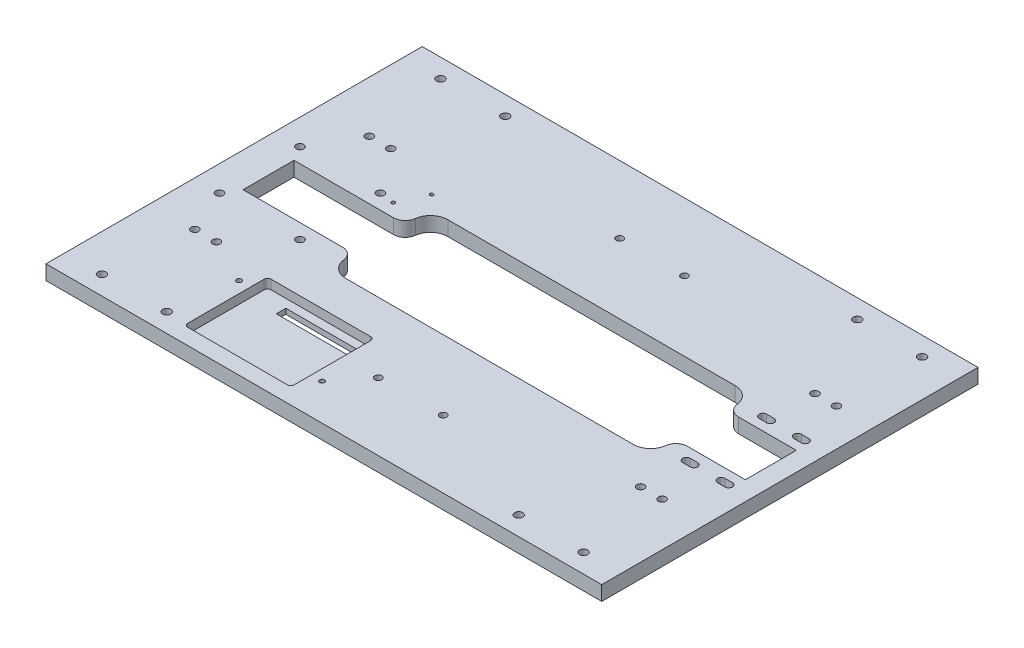
SolidWorks part; units mm, degrees
ref_plane "Front Plane" through (0, 0, 0) normal (0, 0, 1) x (1, 0, 0)
ref_plane "Top Plane" through (0, 0, 0) normal (0, 1, 0) x (1, 0, 0)
ref_plane "Right Plane" through (0, 0, 0) normal (1, 0, 0) x (0, 0, -1)
sketch "Sketch1" plane through (0, 0, 0) normal (0, 1, 0) x (1, 0, 0)
  line L1 (-240, 162.5) -> (240, 162.5)
  line L2 (-240, 162.5) -> (-240, -162.5)
  line L3 (-240, -162.5) -> (240, -162.5)
  line L4 (240, 162.5) -> (240, -162.5)
  line L5 (-240, 162.5) -> (240, -162.5) construction
  line L6 (-240, -162.5) -> (240, 162.5) construction
  point P0 (0, 0)
  dimension "D1" = 480
  dimension "D2" = 325
extrude "Boss-Extrude1" add sketch "Sketch1" along normal blind 12.6
sketch "Sketch2" plane through (0, 0, 0) normal (0, -1, 0) x (1, 0, 0)
  circle A0 centre (44.7486, -104.2) radius 3
  circle A1 centre (-11.2514, -104.2) radius 3
  circle A2 centre (44.7486, 104.2) radius 3
  circle A3 centre (-11.2514, 104.2) radius 3
extrude "Cut-Extrude1" cut sketch "Sketch2" against normal up to next
sketch "Sketch3" plane through (0, 0, 0) normal (0, -1, 0) x (1, 0, 0)
  line L0 (-192.4406, 0) -> (188.5847, 0) construction
  line L1 (163.5847, 44) -> (-114.2887, 44)
  line L2 (163.5847, 44) -> (163.5847, 22)
  line L3 (163.5847, -44) -> (-114.2887, -44)
  line L5 (-114.2887, -44) -> (-114.2887, -22)
  line L6 (-114.2887, -22) -> (-210.2887, -22)
  line L7 (-114.2887, 44) -> (-114.2887, 22)
  line L8 (-114.2887, 22) -> (-210.2887, 22)
  line L9 (-210.2887, 22) -> (-210.2887, -22)
  line L10 (163.5847, 22) -> (223.5847, 22)
  line L11 (223.5847, 22) -> (223.5847, -22)
  line L12 (223.5847, -22) -> (163.5847, -22)
  line L13 (163.5847, -22) -> (163.5847, -44)
  point P0 (0, 0)
  point P1 (-210.2887, 0)
  dimension "D2" = 96
  dimension "D1" = 22
  dimension "D5" = 60
extrude "Cut-Extrude2" cut sketch "Sketch3" against normal up to next
fillet "Fillet1" radius 10 2 edges at (-114.2887, 6.3, 22) (-114.2887, 6.3, -22)
sketch "Sketch4" plane through (0, 0, 0) normal (0, -1, 0) x (1, 0, 0)
  circle A12 centre (-148.4257, -34.75) radius 3.3
  circle A13 centre (-148.4257, 34.75) radius 3.3
  circle A14 centre (-217.9257, 34.75) radius 3.3
  circle A15 centre (-217.9257, -34.75) radius 3.3
extrude "Cut-Extrude3" cut sketch "Sketch4" against normal up to next
fillet "Fillet2" radius 10 2 edges at (163.5847, 6.3, -22) (163.5847, 6.3, 22)
sketch "Sketch7" plane through (0, 12.6, 0) normal (0, 1, 0) x (1, 0, 0)
  circle A0 centre (208, -146.2) radius 2.25
  circle A1 centre (152, -146.2) radius 2.25
  circle A2 centre (-152, -146.2) radius 2.25
  circle A3 centre (-208, -146.2) radius 2.25
  circle A4 centre (-208, 146.2) radius 2.25
  circle A5 centre (-152, 146.2) radius 2.25
  circle A6 centre (208, 146.2) radius 2.25
  circle A7 centre (152, 146.2) radius 2.25
  circle A9 centre (-143.9752, -91.7292) radius 2.2102
  circle A10 centre (-32.9752, -131.1304) radius 2.1044
  dimension "D1" = 4.5
extrude "Cut-Extrude7" cut sketch "Sketch7" against normal up to next
sketch "Sketch8" plane through (0, 12.6, 0) normal (0, 1, 0) x (1, 0, 0)
  circle A0 centre (208, 146.2) radius 3.5
  circle A1 centre (152, 146.2) radius 3.5
  circle A2 centre (-152, 146.2) radius 3.5
  circle A3 centre (-208, 146.2) radius 3.5
  circle A4 centre (208, -146.2) radius 3.5
  circle A5 centre (152, -146.2) radius 3.5
  circle A6 centre (-208, -146.2) radius 3.5
  circle A7 centre (-152, -146.2) radius 3.5
  dimension "D1" = 7
extrude "Cut-Extrude8" cut sketch "Sketch8" against normal blind 6
sketch "Sketch9" plane through (0, 12.6, 0) normal (0, 1, 0) x (1, 0, 0)
  line L1 (-131.2752, -76.7932) -> (-45.2752, -76.7932)
  line L2 (-134.2752, -79.7932) -> (-134.2752, -145.7932)
  line L3 (-131.2752, -148.7932) -> (-45.2752, -148.7932)
  line L4 (-42.2752, -79.7932) -> (-42.2752, -145.7932)
  arc A0 (-134.2752, -145.7932) -> (-131.2752, -148.7932) centre (-131.2752, -145.7932) ccw
  arc A1 (-45.2752, -148.7932) -> (-42.2752, -145.7932) centre (-45.2752, -145.7932) ccw
  arc A2 (-45.2752, -76.7932) -> (-42.2752, -79.7932) centre (-45.2752, -79.7932) cw
  arc A3 (-131.2752, -76.7932) -> (-134.2752, -79.7932) centre (-131.2752, -79.7932) ccw
  dimension "D5" = 3
sketch "Sketch12" plane through (0, 0, 0) normal (0, -1, 0) x (1, 0, 0)
  circle A0 centre (-135.8148, -33.2631) radius 1.5
  circle A1 centre (-125.2148, -55.8631) radius 1.5
extrude "Cut-Extrude11" cut sketch "Sketch12" against normal up to next
fillet "Fillet3" radius 15 4 edges at (163.5847, 6.3, 44) (163.5847, 6.3, -44) (-114.2887, 6.3, 44) (-114.2887, 6.3, -44)
extrude "Cut-Extrude12" cut sketch "Sketch9" against normal blind 8
sketch "Sketch14" plane through (0, 4.6, 0) normal (0, 1, 0) x (1, 0, 0)
  line L1 (-111.1572, -84.1633) -> (-47.573, -84.1633)
  line L2 (-111.1572, -84.1633) -> (-111.1572, -92.4204)
  line L3 (-111.1572, -92.4204) -> (-47.573, -92.4204)
  line L4 (-47.573, -84.1633) -> (-47.573, -92.4204)
extrude "Cut-Extrude13" cut sketch "Sketch14" against normal through all
sketch "Sketch15" plane through (0, 12.6, 0) normal (0, 1, 0) x (1, 0, 0)
  circle A0 centre (-201.3752, -72.5) radius 3.25 construction
  circle A1 centre (-182.8647, -72.5) radius 3.25 construction
  circle A2 centre (-195.7918, 72.5) radius 3.25 construction
  circle A3 centre (-177.2813, 72.5) radius 3.25 construction
  circle A4 centre (189.2082, 72.5) radius 3.25 construction
  circle A5 centre (207.7187, 72.5) radius 3.25 construction
  circle A6 centre (183.6248, -72.5) radius 3.25 construction
  circle A7 centre (202.1353, -72.5) radius 3.25 construction
  circle A8 centre (-201.3752, -72.5) radius 3.25
  circle A9 centre (-182.8647, -72.5) radius 3.25
  circle A10 centre (-195.7918, 72.5) radius 3.25
  circle A11 centre (-177.2813, 72.5) radius 3.25
  circle A12 centre (189.2082, 72.5) radius 3.25
  circle A13 centre (207.7187, 72.5) radius 3.25
  circle A14 centre (183.6248, -72.5) radius 3.25
  circle A15 centre (202.1353, -72.5) radius 3.25
extrude "Cut-Extrude14" cut sketch "Sketch15" against normal up to next
sketch "Sketch16" plane through (0, 12.6, 0) normal (0, 1, 0) x (1, 0, 0)
  line L0 (183.6729, -33) -> (186.9229, -33) construction
  line L1 (213.6729, -33) -> (216.9229, -33) construction
  line L2 (183.6729, 33) -> (186.9229, 33) construction
  line L3 (213.6729, 33) -> (216.9229, 33) construction
  line L4 (183.6729, -36.25) -> (190.1729, -36.25)
  line L5 (183.6729, -29.75) -> (190.1729, -29.75)
  line L6 (213.6729, -36.25) -> (220.1729, -36.25)
  line L7 (213.6729, -29.75) -> (220.1729, -29.75)
  line L8 (183.6729, 29.75) -> (190.1729, 29.75)
  line L9 (183.6729, 36.25) -> (190.1729, 36.25)
  line L10 (213.6729, 29.75) -> (220.1729, 29.75)
  line L11 (213.6729, 36.25) -> (220.1729, 36.25)
  arc A4 (213.6729, -29.75) -> (213.6729, -36.25) centre (213.6729, -33) ccw
  arc A5 (183.6729, -29.75) -> (183.6729, -36.25) centre (183.6729, -33) ccw
  arc A6 (183.6729, 36.25) -> (183.6729, 29.75) centre (183.6729, 33) ccw
  arc A7 (213.6729, 36.25) -> (213.6729, 29.75) centre (213.6729, 33) ccw
  arc A8 (190.1729, -36.25) -> (190.1729, -29.75) centre (190.1729, -33) ccw
  arc A9 (220.1729, -36.25) -> (220.1729, -29.75) centre (220.1729, -33) ccw
  arc A10 (220.1729, 29.75) -> (220.1729, 36.25) centre (220.1729, 33) ccw
  arc A11 (190.1729, 29.75) -> (190.1729, 36.25) centre (190.1729, 33) ccw
  dimension "D1" = 6.5
  dimension "D2" = 6.5
  dimension "D3" = 6.5
  dimension "D4" = 6.5
extrude "Cut-Extrude15" cut sketch "Sketch16" against normal up to next
sketch "Sketch17" plane through (0, 12.6, 0) normal (0, 1, 0) x (1, 0, 0)
  line L4 (240, -162.5) -> (240, 162.5)
  line L5 (240, 162.5) -> (-240, 162.5)
  line L6 (-240, 162.5) -> (-240, -162.5)
  line L7 (-240, -162.5) -> (240, -162.5)
  line L8 (240, -162.5) -> (240, 162.5)
  line L9 (240, 162.5) -> (-240, 162.5)
  line L10 (-240, 162.5) -> (-240, -162.5)
  line L11 (-240, -162.5) -> (240, -162.5)
  line L14 (220.1729, -29.75) -> (213.6729, -29.75)
  line L15 (213.6729, -36.25) -> (220.1729, -36.25)
  line L16 (220.1729, -29.75) -> (213.6729, -29.75)
  line L17 (213.6729, -36.25) -> (220.1729, -36.25)
  line L18 (190.1729, -29.75) -> (183.6729, -29.75)
  line L19 (183.6729, -36.25) -> (190.1729, -36.25)
  line L20 (190.1729, -29.75) -> (183.6729, -29.75)
  line L21 (183.6729, -36.25) -> (190.1729, -36.25)
  line L22 (220.1729, 36.25) -> (213.6729, 36.25)
  line L23 (213.6729, 29.75) -> (220.1729, 29.75)
  line L24 (220.1729, 36.25) -> (213.6729, 36.25)
  line L25 (213.6729, 29.75) -> (220.1729, 29.75)
  line L26 (190.1729, 36.25) -> (183.6729, 36.25)
  line L27 (183.6729, 29.75) -> (190.1729, 29.75)
  line L28 (190.1729, 36.25) -> (183.6729, 36.25)
  line L29 (183.6729, 29.75) -> (190.1729, 29.75)
  line L33 (-134.2752, -79.7932) -> (-134.2752, -145.7932)
  line L34 (-45.2752, -76.7932) -> (-131.2752, -76.7932)
  line L35 (-42.2752, -145.7932) -> (-42.2752, -79.7932)
  line L36 (148.7654, 44) -> (-99.4693, 44)
  line L37 (223.5847, 22) -> (173.5847, 22)
  line L38 (223.5847, -22) -> (223.5847, 22)
  line L39 (173.5847, -22) -> (223.5847, -22)
  line L40 (-99.4693, -44) -> (148.7654, -44)
  line L41 (-210.2887, -22) -> (-124.2887, -22)
  line L42 (-210.2887, 22) -> (-210.2887, -22)
  line L43 (-124.2887, 22) -> (-210.2887, 22)
  line L44 (148.7654, 44) -> (-99.4693, 44)
  line L45 (223.5847, 22) -> (173.5847, 22)
  line L46 (223.5847, -22) -> (223.5847, 22)
  line L47 (173.5847, -22) -> (223.5847, -22)
  line L48 (-99.4693, -44) -> (148.7654, -44)
  line L49 (-210.2887, -22) -> (-124.2887, -22)
  line L50 (-210.2887, 22) -> (-210.2887, -22)
  line L51 (-124.2887, 22) -> (-210.2887, 22)
  line L52 (-131.2752, -148.7932) -> (-45.2752, -148.7932)
  line L53 (-134.2752, -79.7932) -> (-134.2752, -145.7932)
  line L54 (-45.2752, -76.7932) -> (-131.2752, -76.7932)
  line L55 (-42.2752, -145.7932) -> (-42.2752, -79.7932)
  line L56 (-131.2752, -148.7932) -> (-45.2752, -148.7932)
  line L58 (-111.1572, -84.1633) -> (-111.1572, -92.4204)
  line L59 (-47.573, -84.1633) -> (-111.1572, -84.1633)
  line L60 (-47.573, -92.4204) -> (-47.573, -84.1633)
  line L61 (-111.1572, -92.4204) -> (-47.573, -92.4204)
  line L62 (-111.1572, -84.1633) -> (-111.1572, -92.4204)
  line L63 (-47.573, -84.1633) -> (-111.1572, -84.1633)
  line L64 (-47.573, -92.4204) -> (-47.573, -84.1633)
  line L65 (-111.1572, -92.4204) -> (-47.573, -92.4204)
  circle A0 centre (208, 146.2) radius 3.5 construction
  circle A1 centre (208, 146.2) radius 2.25 construction
  circle A2 centre (152, 146.2) radius 3.5 construction
  circle A3 centre (152, 146.2) radius 2.25 construction
  circle A4 centre (-11.2514, 104.2) radius 3 construction
  circle A5 centre (44.7486, 104.2) radius 3 construction
  circle A6 centre (207.7187, 72.5) radius 3.25 construction
  circle A7 centre (189.2082, 72.5) radius 3.25 construction
  circle A8 centre (202.1353, -72.5) radius 3.25 construction
  circle A9 centre (183.6248, -72.5) radius 3.25 construction
  circle A10 centre (208, -146.2) radius 3.5 construction
  circle A11 centre (208, -146.2) radius 2.25 construction
  circle A12 centre (152, -146.2) radius 3.5 construction
  circle A13 centre (152, -146.2) radius 2.25 construction
  circle A14 centre (44.7486, -104.2) radius 3 construction
  circle A15 centre (-11.2514, -104.2) radius 3 construction
  circle A16 centre (-152, -146.2) radius 2.25 construction
  circle A17 centre (-152, -146.2) radius 3.5 construction
  circle A18 centre (-208, -146.2) radius 3.5 construction
  circle A19 centre (-208, -146.2) radius 2.25 construction
  circle A20 centre (-182.8647, -72.5) radius 3.25 construction
  circle A21 centre (-201.3752, -72.5) radius 3.25 construction
  circle A22 centre (-217.9257, -34.75) radius 3.3 construction
  circle A23 centre (-148.4257, -34.75) radius 3.3 construction
  circle A24 centre (-125.2148, 55.8631) radius 1.5 construction
  circle A25 centre (-135.8148, 33.2631) radius 1.5 construction
  circle A26 centre (-148.4257, 34.75) radius 3.3 construction
  circle A27 centre (-217.9257, 34.75) radius 3.3 construction
  circle A28 centre (-177.2813, 72.5) radius 3.25 construction
  circle A29 centre (-195.7918, 72.5) radius 3.25 construction
  circle A30 centre (-152, 146.2) radius 2.25 construction
  circle A31 centre (-152, 146.2) radius 3.5 construction
  circle A32 centre (-208, 146.2) radius 2.25 construction
  circle A33 centre (-208, 146.2) radius 3.5 construction
  circle A34 centre (208, 146.2) radius 3.5
  circle A35 centre (208, 146.2) radius 2.25
  circle A36 centre (152, 146.2) radius 3.5
  circle A37 centre (152, 146.2) radius 2.25
  circle A38 centre (-11.2514, 104.2) radius 3
  circle A39 centre (44.7486, 104.2) radius 3
  circle A40 centre (207.7187, 72.5) radius 3.25
  circle A41 centre (189.2082, 72.5) radius 3.25
  circle A42 centre (202.1353, -72.5) radius 3.25
  circle A43 centre (183.6248, -72.5) radius 3.25
  circle A44 centre (208, -146.2) radius 3.5
  circle A45 centre (208, -146.2) radius 2.25
  circle A46 centre (152, -146.2) radius 3.5
  circle A47 centre (152, -146.2) radius 2.25
  circle A48 centre (44.7486, -104.2) radius 3
  circle A49 centre (-11.2514, -104.2) radius 3
  circle A50 centre (-152, -146.2) radius 2.25
  circle A51 centre (-152, -146.2) radius 3.5
  circle A52 centre (-208, -146.2) radius 3.5
  circle A53 centre (-208, -146.2) radius 2.25
  circle A54 centre (-182.8647, -72.5) radius 3.25
  circle A55 centre (-201.3752, -72.5) radius 3.25
  circle A56 centre (-217.9257, -34.75) radius 3.3
  circle A57 centre (-148.4257, -34.75) radius 3.3
  circle A58 centre (-125.2148, 55.8631) radius 1.5
  circle A59 centre (-135.8148, 33.2631) radius 1.5
  circle A60 centre (-148.4257, 34.75) radius 3.3
  circle A61 centre (-217.9257, 34.75) radius 3.3
  circle A62 centre (-177.2813, 72.5) radius 3.25
  circle A63 centre (-195.7918, 72.5) radius 3.25
  circle A64 centre (-152, 146.2) radius 2.25
  circle A65 centre (-152, 146.2) radius 3.5
  circle A66 centre (-208, 146.2) radius 2.25
  circle A67 centre (-208, 146.2) radius 3.5
  circle A68 centre (-32.9752, -131.1304) radius 2.1044 construction
  circle A69 centre (-143.9752, -91.7292) radius 2.2102 construction
  arc A70 (213.6729, -29.75) -> (213.6729, -36.25) centre (213.6729, -33) ccw
  arc A71 (220.1729, -36.25) -> (220.1729, -29.75) centre (220.1729, -33) ccw
  arc A72 (213.6729, -29.75) -> (213.6729, -36.25) centre (213.6729, -33) ccw
  arc A73 (220.1729, -36.25) -> (220.1729, -29.75) centre (220.1729, -33) ccw
  arc A74 (183.6729, -29.75) -> (183.6729, -36.25) centre (183.6729, -33) ccw
  arc A75 (190.1729, -36.25) -> (190.1729, -29.75) centre (190.1729, -33) ccw
  arc A76 (183.6729, -29.75) -> (183.6729, -36.25) centre (183.6729, -33) ccw
  arc A77 (190.1729, -36.25) -> (190.1729, -29.75) centre (190.1729, -33) ccw
  arc A78 (213.6729, 36.25) -> (213.6729, 29.75) centre (213.6729, 33) ccw
  arc A79 (220.1729, 29.75) -> (220.1729, 36.25) centre (220.1729, 33) ccw
  arc A80 (213.6729, 36.25) -> (213.6729, 29.75) centre (213.6729, 33) ccw
  arc A81 (220.1729, 29.75) -> (220.1729, 36.25) centre (220.1729, 33) ccw
  arc A82 (183.6729, 36.25) -> (183.6729, 29.75) centre (183.6729, 33) ccw
  arc A83 (190.1729, 29.75) -> (190.1729, 36.25) centre (190.1729, 33) ccw
  arc A84 (183.6729, 36.25) -> (183.6729, 29.75) centre (183.6729, 33) ccw
  arc A85 (190.1729, 29.75) -> (190.1729, 36.25) centre (190.1729, 33) ccw
  circle A86 centre (-32.9752, -131.1304) radius 2.1044
  circle A87 centre (-143.9752, -91.7292) radius 2.2102
  arc A88 (-134.2752, -145.7932) -> (-131.2752, -148.7932) centre (-131.2752, -145.7932) ccw
  arc A89 (-131.2752, -76.7932) -> (-134.2752, -79.7932) centre (-131.2752, -79.7932) ccw
  arc A90 (-42.2752, -79.7932) -> (-45.2752, -76.7932) centre (-45.2752, -79.7932) ccw
  arc A91 (-45.2752, -148.7932) -> (-42.2752, -145.7932) centre (-45.2752, -145.7932) ccw
  arc A92 (163.657, 30.8) -> (148.7654, 44) centre (148.7654, 29) ccw
  arc A93 (163.657, 30.8) -> (173.5847, 22) centre (173.5847, 32) ccw
  arc A94 (173.5847, -22) -> (163.657, -30.8) centre (173.5847, -32) ccw
  arc A95 (148.7654, -44) -> (163.657, -30.8) centre (148.7654, -29) ccw
  arc A96 (-114.3609, -30.8) -> (-99.4693, -44) centre (-99.4693, -29) ccw
  arc A97 (-114.3609, -30.8) -> (-124.2887, -22) centre (-124.2887, -32) ccw
  arc A98 (-124.2887, 22) -> (-114.3609, 30.8) centre (-124.2887, 32) ccw
  arc A99 (-99.4693, 44) -> (-114.3609, 30.8) centre (-99.4693, 29) ccw
  arc A100 (163.657, 30.8) -> (148.7654, 44) centre (148.7654, 29) ccw
  arc A101 (163.657, 30.8) -> (173.5847, 22) centre (173.5847, 32) ccw
  arc A102 (173.5847, -22) -> (163.657, -30.8) centre (173.5847, -32) ccw
  arc A103 (148.7654, -44) -> (163.657, -30.8) centre (148.7654, -29) ccw
  arc A104 (-114.3609, -30.8) -> (-99.4693, -44) centre (-99.4693, -29) ccw
  arc A105 (-114.3609, -30.8) -> (-124.2887, -22) centre (-124.2887, -32) ccw
  arc A106 (-124.2887, 22) -> (-114.3609, 30.8) centre (-124.2887, 32) ccw
  arc A107 (-99.4693, 44) -> (-114.3609, 30.8) centre (-99.4693, 29) ccw
  arc A108 (-134.2752, -145.7932) -> (-131.2752, -148.7932) centre (-131.2752, -145.7932) ccw
  arc A109 (-131.2752, -76.7932) -> (-134.2752, -79.7932) centre (-131.2752, -79.7932) ccw
  arc A110 (-42.2752, -79.7932) -> (-45.2752, -76.7932) centre (-45.2752, -79.7932) ccw
  arc A111 (-45.2752, -148.7932) -> (-42.2752, -145.7932) centre (-45.2752, -145.7932) ccw
  dimension "D1" = 0
  dimension "D2" = 0
  dimension "D3" = 0
  dimension "D4" = 0
  dimension "D5" = 0
  dimension "D6" = 0
  dimension "D7" = 0
  dimension "D8" = 0
